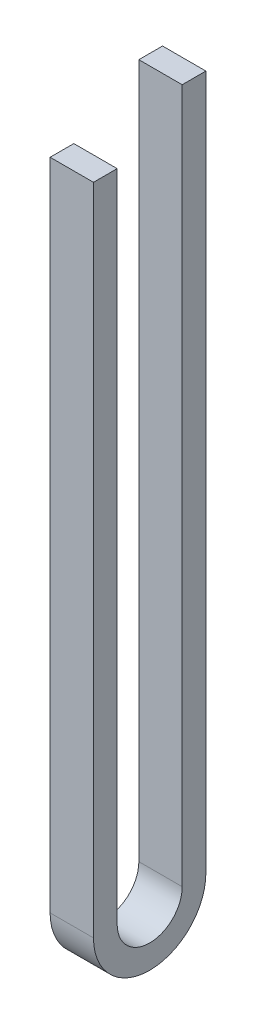
SolidWorks part; units mm, degrees
ref_plane "Front" through (0, 0, 0) normal (0, 0, 1) x (1, 0, 0)
ref_plane "Top" through (0, 0, 0) normal (0, 1, 0) x (1, 0, 0)
ref_plane "Right" through (0, 0, 0) normal (1, 0, 0) x (0, 0, -1)
sketch "Sketch1" plane through (0, 0, 0) normal (1, 0, 0) x (0, 0, -1)
  line L0 (0, 0) -> (0, -414.0425)
  line L1 (71.12, -414.0425) -> (71.12, 25.4)
  line L2 (14.986, 0) -> (14.986, -414.0425)
  line L3 (56.134, -414.0425) -> (56.134, 25.4)
  line L4 (0, 0) -> (14.986, 0)
  line L5 (56.134, 25.4) -> (71.12, 25.4)
  line L7 (2.54, 25.4) -> (73.025, 25.4) construction
  arc A0 (0, -414.0425) -> (71.12, -414.0425) centre (35.56, -414.0425) ccw
  arc A1 (14.986, -414.0425) -> (56.134, -414.0425) centre (35.56, -414.0425) ccw
  dimension "D1" = 965.2
  dimension "D2" = 71.12
  dimension "D4" = 41.148
  dimension "D3" = 14.986
extrude "Boss-Extrude1" add sketch "Sketch1" along normal blind 27.432
